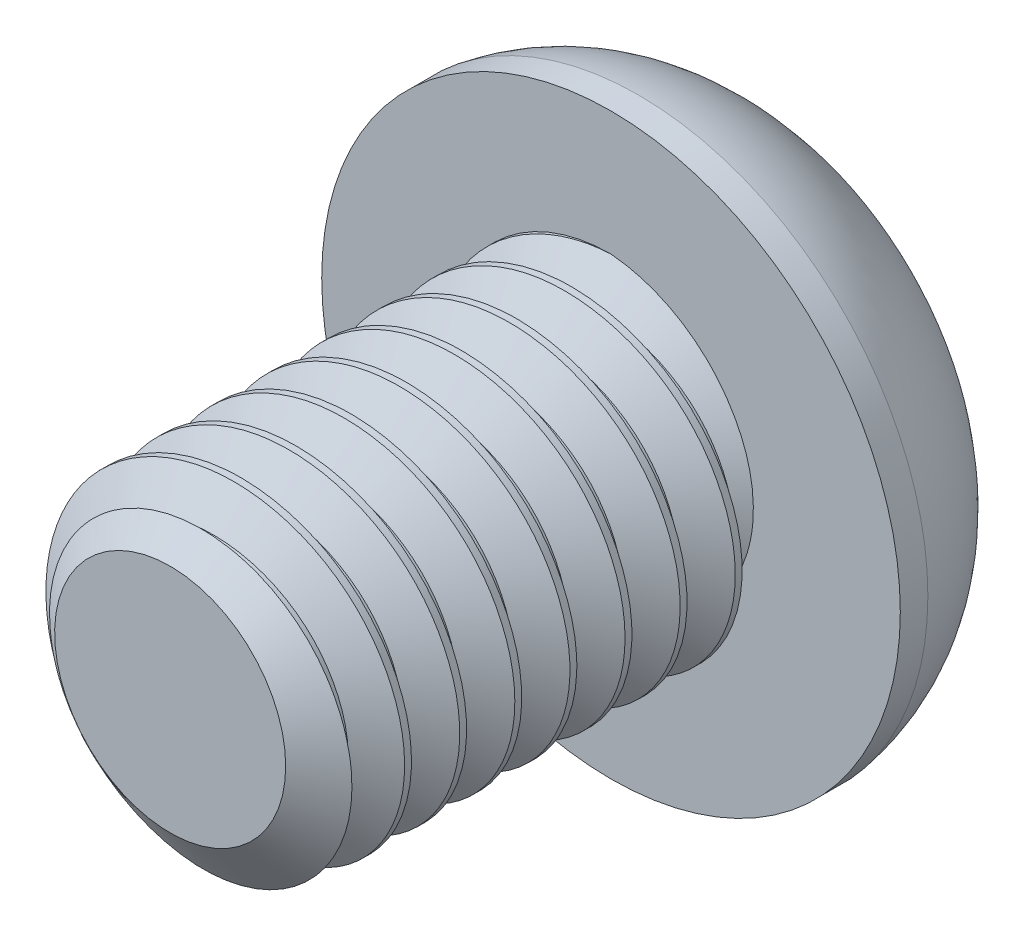
SolidWorks part; units mm, degrees
material "AISI 304"
ref_plane "Front Plane" through (0, 0, 0) normal (0, 0, 1) x (1, 0, 0)
ref_plane "Top Plane" through (0, 0, 0) normal (0, 1, 0) x (1, 0, 0)
ref_plane "Right Plane" through (0, 0, 0) normal (1, 0, 0) x (0, 0, -1)
sketch "Sketch1" plane through (0, 0, 0) normal (0, 0, 1) x (1, 0, 0)
  circle A0 centre (0, 0) radius 3
  dimension "OD" = 6
extrude "Extrude1" add sketch "Sketch1" against normal blind 8
sketch "Sketch2" plane through (0, 0, 0) normal (0, 0, 1) x (1, 0, 0)
  circle A0 centre (0, 0) radius 3 construction
  circle A1 centre (0, 0) radius 3
curve "Helix/Spiral1" pitch 1 height 9 turns 9 parameters "pitch"=1
sketch "Sketch3" plane through (0, 0, 0) normal (1, 0, 0) x (0, 0, -1)
  line L0 (-0.875, 3) -> (-0.5, 2.3505)
  line L1 (-0.5, 2.3505) -> (-0.375, 2.3505)
  line L2 (-0.375, 2.3505) -> (0, 3)
  line L3 (-0.875, 3) -> (0, 3)
  line L4 (-0.4375, 3) -> (-0.4375, 2.3505) construction
  line L5 (-0.6875, 2.6752) -> (-0.1875, 2.6752) construction
  line L6 (0, 3) -> (0, -3) construction
  dimension "D1" = 0.125
  dimension "D2" = 0.5
  dimension "D3" = 60
sweep "Cut-Sweep1" cut profiles "Sketch3" path "Helix/Spiral1"
sketch "Sketch4" plane through (0, 0, 0) normal (1, 0, 0) x (0, 0, -1)
  line L0 (0.6327, 3) -> (0, 2.0965)
  line L1 (0, 2.0965) -> (0, 3)
  line L2 (0.6327, 3) -> (0, 3)
  line L3 (-0.875, 3) -> (0, 3) construction
  line L4 (0, 0) -> (7.0209, 0) construction
  dimension "D1" = 55
  dimension "D2" = 0.254
revolve "Cut-Revolve1" cut sketch "Sketch4" angle 360 about L4
sketch "Sketch5" plane through (0, 0, 0) normal (1, 0, 0) x (0, 0, -1)
  line L0 (8, -2.3644) -> (8, 2.1406) construction
  line L1 (8, 3.127) -> (28.1202, 3.127)
  line L2 (8, 3.127) -> (8, 0)
  line L3 (8, 0) -> (28, 0)
  line L4 (28, 2.7968) -> (28, 0)
  line L5 (28.1202, 3.127) -> (28, 2.7968)
  line L6 (0, 0) -> (9.9695, 0) construction
  point P3 (28, 3.127)
  point P10 (28, 3.127)
  dimension "D1" = 0.3302
  dimension "Thread min" = 28
  dimension "D2" = 0.127
  dimension "D3" = 20
revolve "partially thread" [suppressed] add sketch "Sketch5" angle 360 about L6
sketch "Sketch6" plane through (0, 0, -8) normal (0, 0, -1) x (-1, 0, 0)
  circle A0 centre (0, 0) radius 5.25
  dimension "head dia" = 10.5
extrude "Extrude2" add sketch "Sketch6" along normal blind 3.3
sketch "Sketch10" plane through (0, 0, 0) normal (1, 0, 0) x (0, 0, -1)
  line L0 (11.3, -5.25) -> (11.3, 5.25) construction
  line L1 (0, 0) -> (15.9584, 0) construction
  line L2 (11.3, 5.25) -> (8, 5.25) construction
  line L3 (8, 5.25) -> (8, -5.25) construction
  line L4 (8.5, 5.25) -> (8.5, 5.75)
  line L5 (8.5, 5.75) -> (11.8, 5.75)
  line L6 (11.8, 5.75) -> (11.8, 2)
  line L7 (11.3, 2) -> (11.8, 2)
  arc A0 (11.3, 2) -> (8.5, 5.25) centre (8.0138, 2) ccw
  dimension "D1" = 4
  dimension "D2" = 0.5
  dimension "D3" = 0.5
revolve "Cut-Revolve2" cut sketch "Sketch10" angle 360 about L1
ref_plane "Plane1" through (0, 0, -11.3) normal (0, 0, 1) x (1, 0, 0)
sketch "Sketch7" plane through (0, 0, -11.3) normal (0, 0, -1) x (-1, 0, 0)
  line L1 (0, 2.3094) -> (-2, 1.1547)
  line L2 (-2, 1.1547) -> (-2, -1.1547)
  line L3 (-2, -1.1547) -> (0, -2.3094)
  line L4 (0, -2.3094) -> (2, -1.1547)
  line L5 (2, -1.1547) -> (2, 1.1547)
  line L6 (2, 1.1547) -> (0, 2.3094)
  circle A0 centre (0, 0) radius 2 construction
  dimension "hex dia" = 4
extrude "Cut-Extrude1" cut sketch "Sketch7" against normal blind 3
sketch "Sketch8" plane through (0, 0, -11.3) normal (0, 0, 1) x (1, 0, 0)
  circle A0 centre (0, 0) radius 2.3094
extrude "Cut-Extrude2" cut sketch "Sketch8" along normal through all draft 45
sketch "Sketch9" plane through (0, 0, 0) normal (1, 0, 0) x (0, 0, -1)
  line L0 (0, 3) -> (0, -3) construction
  line L1 (5.5, 3) -> (5.5, -3) construction
  dimension "D1" = 5.5
equation "\"D3@Helix/Spiral1\" = \"screw length@Extrude1\"+\"pitch@Helix/Spiral1\""
equation "\"D1@Sketch3\" = \"pitch@Helix/Spiral1\"*.125"
equation "\"D2@Sketch3\" = \"pitch@Helix/Spiral1\"*.5"
equation "\"D1@Cut-Extrude1\" = \"hex dia@Sketch7\"*.75"
equation "\"D1@Sketch9\" = \"pitch@Helix/Spiral1\"*5.5"
equation "\"D1@Sketch10\" = \"hex dia@Sketch7\""
equation "\"D1@Plane1\" = \"head depth@Extrude2\""
